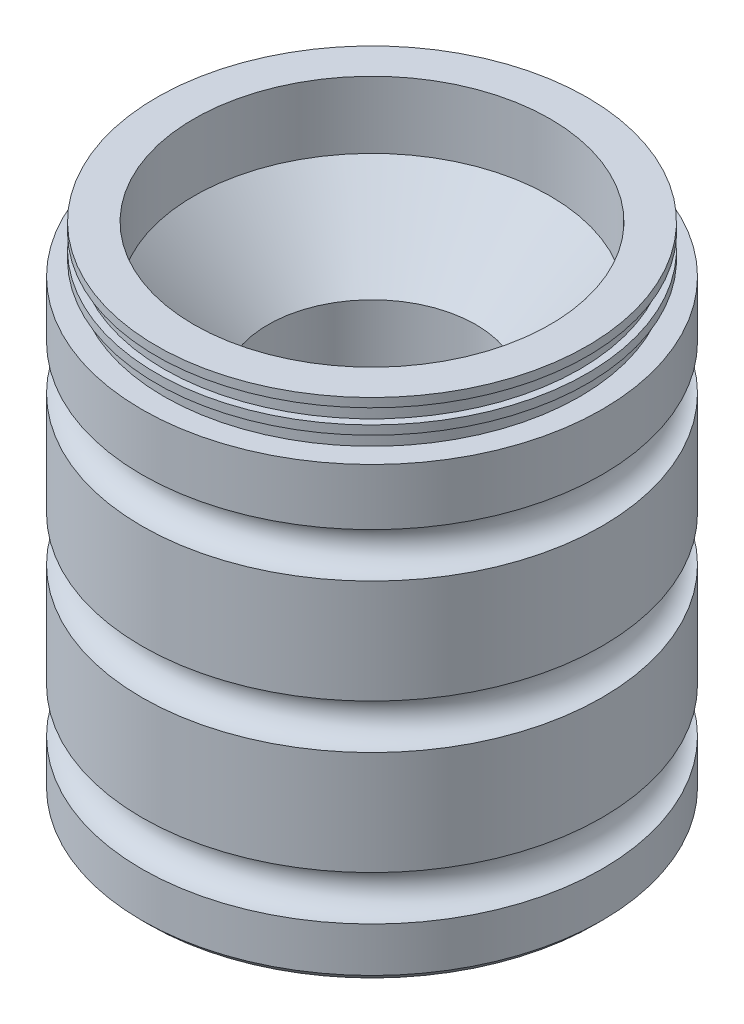
SolidWorks part; units mm, degrees
material "AISI 316 Barre d'acier inoxydable recuit (SS)"
ref_plane "Plan de face" through (0, 0, 0) normal (0, 0, 1) x (1, 0, 0)
ref_plane "Plan de dessus" through (0, 0, 0) normal (0, 1, 0) x (1, 0, 0)
ref_plane "Plan de droite" through (0, 0, 0) normal (1, 0, 0) x (0, 0, -1)
sketch "Esquisse1" plane through (0, 0, 0) normal (0, 0, 1) x (1, 0, 0)
  line L0 (0, -29.1154) -> (0, 30.7029) construction
  line L4 (-7, 24) -> (-7, 3) construction
  line L5 (-7, 3) -> (0, 3) construction
  line L9 (0, 0) -> (-15.5, 0)
  line L10 (-15.5, 0) -> (-15.5, 30.3) construction
  line L11 (-7, 24) -> (-12, 29)
  line L13 (-14.5, 27.2574) -> (-14.5, 33.5) construction
  line L14 (-14.5, 33.5) -> (-12, 33.5)
  line L17 (-12, 33.5) -> (-12, 29)
  line L18 (-14.5, 33.5) -> (-14.5, 32.9)
  line L19 (-14.5, 32.9) -> (-14, 32.9)
  line L20 (-14, 32.9) -> (-14, 31.9)
  line L21 (-14, 31.9) -> (-14.5, 31.9)
  line L22 (-14.5, 31.9) -> (-14.5, 31.3)
  line L23 (-14.5, 31.3) -> (-14, 31.3)
  line L24 (-14, 31.3) -> (-14, 30.3)
  line L29 (-14, 30.3) -> (-14.5, 30.3)
  line L33 (-15.5, 30.3) -> (-14.5, 30.3)
  line L34 (0, 3) -> (0, 0)
  line L35 (-15.5, 30.3) -> (-15.5, 26.5)
  line L36 (-15.5, 23.5) -> (-15.5, 16.5)
  line L37 (-15.5, 13.5) -> (-15.5, 6.5)
  line L38 (-15.5, 3.5) -> (-15.5, 0)
  line L39 (-7, 24) -> (-7, 8)
  line L40 (-7, 8) -> (0, 6)
  line L41 (0, 6) -> (0, 3)
  arc A0 (-15.5, 26.5) -> (-15.5, 23.5) centre (-15.5, 25) cw
  arc A1 (-15.5, 16.5) -> (-15.5, 13.5) centre (-15.5, 15) cw
  arc A2 (-15.5, 6.5) -> (-15.5, 3.5) centre (-15.5, 5) cw
  point P15 (0, 0)
  point P25 (-13.9712, 31.8)
  dimension "D5" = 1.5
  dimension "D1" = 7
  dimension "D2" = 15.5
  dimension "D3" = 12
  dimension "D4" = 33.5
  dimension "D6" = 3
  dimension "D7" = 10
  dimension "D8" = 5
  dimension "D10" = 1.5
  dimension "45" = 45
  dimension "D11" = 5
  dimension "D13" = 21
  dimension "D14" = 1
  dimension "D15" = 0.5
  dimension "D16" = 3
  dimension "D17" = 0.6
revolve "Révolution1" add sketch "Esquisse1" angle 360 about L0
sketch "Esquisse2" plane through (0, 0, 0) normal (0, -1, 0) x (1, 0, 0)
  line L0 (0, 0) -> (15.5, 0) construction
  circle A1 centre (10, 0) radius 2.1
  circle A2 centre (-5, -8.6603) radius 2.1
  circle A3 centre (-5, 8.6603) radius 2.1
  circle A4 centre (0, 0) radius 2
  circle A5 centre (0, 0) radius 15.5 construction
  point P3 (15, 0)
  point P8 (0, 0)
  point P14 (0, 0)
  dimension "D1" = 4.2
  dimension "D4" = 4
  dimension "D2" = 10
  dimension "D3" = 3
extrude "Enlèv. mat.-Extru.1" cut sketch "Esquisse2" against normal blind 15
chamfer "Chanfrein2" distance 0.5 angle 45 4 edges at (-5, 0, -10.7603) (10, 0, -2.1) (0, 0, -2) (-5, 0, 6.5603)
chamfer "Chanfrein3" distance 0.5 angle 45 1 edges at (0, 0, -15.5)
chamfer "Chanfrein4" distance 0.5 angle 45 1 edges at (0, 6.5714, 2) first distance on face at (0, 0.5, 2)
